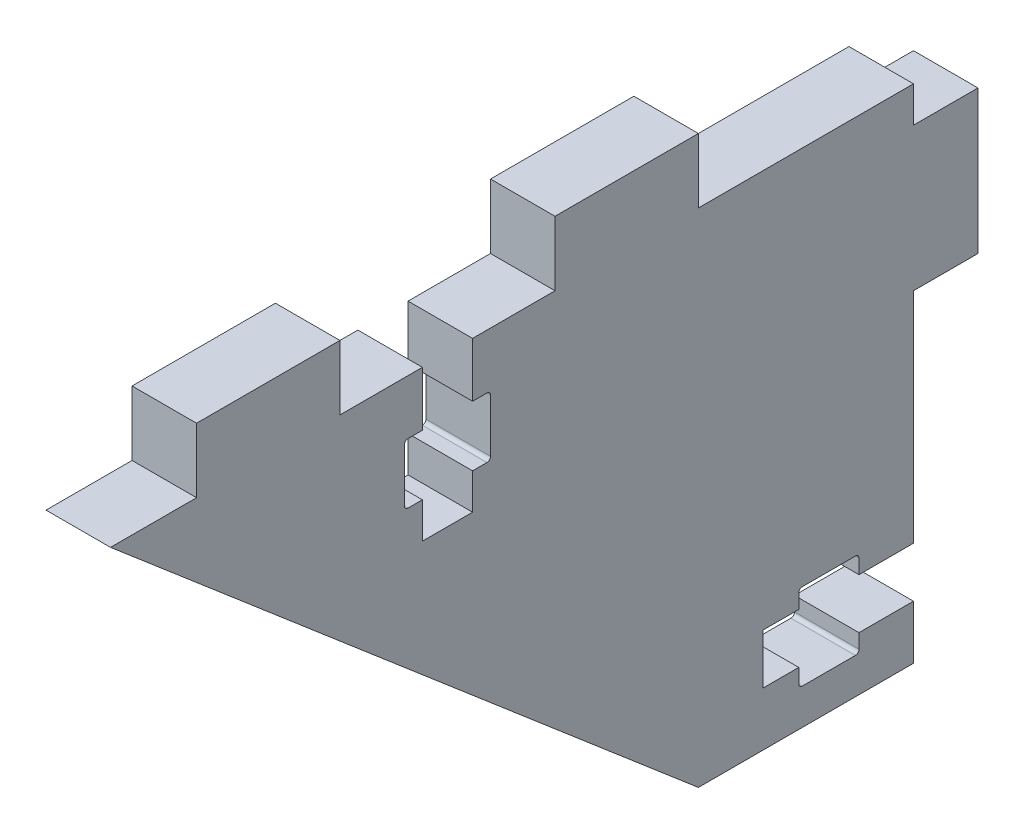
SolidWorks part; units mm, degrees
ref_plane "Front Plane" through (0, 0, 0) normal (0, 0, 1) x (1, 0, 0)
ref_plane "Top Plane" through (0, 0, 0) normal (0, 1, 0) x (1, 0, 0)
ref_plane "Right Plane" through (0, 0, 0) normal (1, 0, 0) x (0, 0, -1)
sketch "Sketch1" plane through (0, 0, 0) normal (1, 0, 0) x (0, 0, -1)
  line L0 (0, 0) -> (0, -35)
  line L1 (0, -35) -> (-56, 0)
  line L2 (-56, 0) -> (0, 0)
  dimension "D1" = 35
  dimension "D2" = 56
extrude "Boss-Extrude1" add sketch "Sketch1" along normal blind 4.5
sketch "Sketch2" plane through (4.5, 0, 0) normal (1, 0, 0) x (0, 0, -1)
  line L0 (0, -35) -> (0, 0) construction
  line L1 (-4.5, -2.5) -> (4.5, -2.5)
  line L2 (-4.5, -2.5) -> (-4.5, -12.5)
  line L3 (-4.5, -12.5) -> (4.5, -12.5)
  line L4 (4.5, -2.5) -> (4.5, -12.5)
  line L5 (-4.5, -2.5) -> (4.5, -12.5) construction
  line L6 (-4.5, -12.5) -> (4.5, -2.5) construction
  line L7 (0, 0) -> (-56, 0) construction
  point P0 (0, -7.5)
  dimension "D1" = 10
  dimension "D2" = 7.5
  dimension "D3" = 4.5
extrude "Boss-Extrude2" add sketch "Sketch2" against normal through all
sketch "Sketch3" plane through (4.5, 0, 0) normal (1, 0, 0) x (0, 0, -1)
  line L0 (0, -35) -> (-15, -35)
  line L1 (0, -25) -> (-56, 0)
  line L4 (0, -35) -> (0, -12.5) construction
  line L5 (0, -25) -> (0, -35)
  line L6 (-56, 0) -> (-15, -35)
  dimension "D1" = 15
  dimension "D2" = 10
extrude "Boss-Extrude3" add sketch "Sketch3" against normal through all
sketch "Sketch4" plane through (4.5, 0, 0) normal (1, 0, 0) x (0, 0, -1)
  line L0 (0, -29.5) -> (-10.5, -29.5) construction
  line L1 (0, -35) -> (0, -12.5) construction
  line L2 (0, -27.75) -> (-10.5, -27.75) construction
  line L3 (-10.5, -27.75) -> (-10.5, -31.25) construction
  line L4 (0, -31.25) -> (0, -27.75)
  line L5 (0, -27.75) -> (-3.8, -27.75)
  line L6 (-3.8, -27.75) -> (-3.8, -26.75)
  line L7 (-4.05, -26.5) -> (-7.75, -26.5)
  line L8 (-8, -26.75) -> (-8, -27.75)
  line L9 (-8, -27.75) -> (-10.5, -27.75)
  line L10 (-10.5, -27.75) -> (-10.5, -31.25)
  line L12 (0, -31.25) -> (-10.5, -31.25) construction
  line L13 (-8, -31.25) -> (-10.5, -31.25)
  line L14 (-8, -32.25) -> (-8, -31.25)
  line L15 (-4.05, -32.5) -> (-7.75, -32.5)
  line L16 (-3.8, -31.25) -> (-3.8, -32.25)
  line L17 (0, -31.25) -> (-3.8, -31.25)
  line L18 (4.5, -12.5) -> (4.5, -2.5) construction
  line L19 (0, -18.5) -> (-34.3286, -18.5) construction
  line L20 (-56, 0) -> (-15, -35) construction
  line L37 (0, -31.25) -> (-10.5, -31.25) construction
  arc A0 (-8, -32.25) -> (-7.75, -32.5) centre (-7.75, -32.25) ccw
  arc A1 (-4.05, -32.5) -> (-3.8, -32.25) centre (-4.05, -32.25) ccw
  arc A2 (-3.8, -26.75) -> (-4.05, -26.5) centre (-4.05, -26.75) ccw
  arc A3 (-7.75, -26.5) -> (-8, -26.75) centre (-7.75, -26.75) ccw
  point P10 (4.5, -7.5)
  point P20 (-8, -32.5)
  point P23 (-3.8, -32.5)
  point P26 (-3.8, -26.5)
  point P29 (-8, -26.5)
  dimension "D7" = 0.25
  dimension "D1" = 10.5
  dimension "D2" = 1.75
  dimension "D3" = 3
  dimension "D4" = 4.2
  dimension "D5" = 8
  dimension "D6" = 22
extrude "Cut-Extrude1" cut sketch "Sketch4" against normal through all
sketch "Sketch5" plane through (4.5, 0, 0) normal (1, 0, 0) x (0, 0, -1)
  line L0 (0, 0) -> (-56, 0) construction
  line L1 (-25, 4.5) -> (-15, 4.5)
  line L2 (-25, 4.5) -> (-25, -4.5)
  line L3 (-25, -4.5) -> (-15, -4.5)
  line L4 (-15, 4.5) -> (-15, -4.5)
  line L5 (-25, 4.5) -> (-15, -4.5) construction
  line L6 (-25, -4.5) -> (-15, 4.5) construction
  line L7 (-32.5, 0) -> (-32.5, 4.5) construction
  line L8 (-40, -4.5) -> (-50, 4.5) construction
  line L9 (-40, 4.5) -> (-50, -4.5) construction
  line L10 (-50, 4.5) -> (-50, -4.5)
  line L11 (-40, -4.5) -> (-50, -4.5)
  line L12 (-40, 4.5) -> (-40, -4.5)
  line L13 (-40, 4.5) -> (-50, 4.5)
  line L14 (-25, -4.5) -> (-15, 4.5) construction
  point P0 (-20, 0)
  point P14 (-45, 0)
  dimension "D3" = 4.5
  dimension "D1" = 20
  dimension "D2" = 10
  dimension "D4" = 25
extrude "Boss-Extrude4" add sketch "Sketch5" against normal through all
sketch "Sketch6" plane through (4.5, 0, 0) normal (1, 0, 0) x (0, 0, -1)
  line L0 (-32.5, 0) -> (-32.5, -10.5) construction
  line L1 (-25, 0) -> (-40, 0) construction
  line L2 (-30.75, -10.5) -> (-34.25, -10.5) construction
  line L3 (-34.25, -10.5) -> (-34.25, 0) construction
  line L4 (-30.75, 0) -> (-34.25, 0)
  line L5 (-34.25, 0) -> (-34.25, -3.8)
  line L6 (-34.25, -3.8) -> (-35.25, -3.8)
  line L7 (-35.5, -4.05) -> (-35.5, -7.75)
  line L8 (-35.25, -8) -> (-34.25, -8)
  line L9 (-34.25, -8) -> (-34.25, -10.5)
  line L10 (-34.25, -10.5) -> (-30.75, -10.5)
  line L11 (-30.75, -10.5) -> (-30.75, 0) construction
  line L12 (-30.75, -8) -> (-30.75, -10.5)
  line L13 (-29.75, -8) -> (-30.75, -8)
  line L14 (-29.5, -4.05) -> (-29.5, -7.75)
  line L15 (-30.75, -3.8) -> (-29.75, -3.8)
  line L16 (-30.75, 0) -> (-30.75, -3.8)
  arc A0 (-35.5, -7.75) -> (-35.25, -8) centre (-35.25, -7.75) ccw
  arc A1 (-35.25, -3.8) -> (-35.5, -4.05) centre (-35.25, -4.05) ccw
  arc A2 (-29.75, -3.8) -> (-29.5, -4.05) centre (-29.75, -4.05) cw
  arc A3 (-29.5, -7.75) -> (-29.75, -8) centre (-29.75, -7.75) cw
  point P12 (-35.5, -8)
  point P15 (-35.5, -3.8)
  point P26 (-29.5, -3.8)
  point P27 (-29.5, -8)
  dimension "D1" = 10.5
  dimension "D2" = 1.75
  dimension "D4" = 4.2
  dimension "D6" = 0.25
  dimension "D3" = 8
  dimension "D5" = 3
extrude "Cut-Extrude2" cut sketch "Sketch6" against normal through all
sketch "Sketch8" [suppressed] plane through (4.5, 0, 0) normal (1, 0, 0) x (0, 0, -1)
  line L0 (-15, -30) -> (-27, -30) construction
  line L1 (-15, -35) -> (-27, -35)
  line L2 (-15, -25) -> (-27, -25)
  line L3 (-15, -35) -> (0, -35) construction
  line L4 (-15, -25) -> (-15, -35)
  arc A1 (-27, -25) -> (-27, -35) centre (-27, -30) ccw
  dimension "D5" = 5
  dimension "D1" = 0
  dimension "D2" = 12
  dimension "D3" = 0
  dimension "D4" = 10
extrude "Boss-Extrude5" [suppressed] add sketch "Sketch8" against normal up to surface (4.5 mm away) up to face at (0, -13.4542, 19.4542)
sketch "Sketch9" [suppressed] plane through (4.5, 0, 0) normal (1, 0, 0) x (0, 0, -1)
  line L0 (-27, -30) -> (-22, -30) construction
  line L1 (-27, -27) -> (-22, -27)
  line L2 (-27, -33) -> (-22, -33)
  arc A0 (-27, -27) -> (-27, -33) centre (-27, -30) ccw
  arc A1 (-22, -33) -> (-22, -27) centre (-22, -30) ccw
  point P3 (-24.5, -30)
  dimension "D1" = 3
  dimension "D2" = 5
extrude "Cut-Extrude3" [suppressed] cut sketch "Sketch9" against normal through all
equation "\"X-ROD-SPACING\"=45"
equation "\"Y-ROD-SPACING\"=75"
equation "\"Z-ROD-SPACING\"=17.5"
equation "\"Y-BED-OFFSET\"=2"
equation "\"Y-BED-ROD-INSET\"=3.5"
equation "\"Y-BED-SCREW-SPACING\"=209"
equation "\"Y-BED-SCREW-CUTOUT-SLOT-HEIGHT\"=1"
equation "\"T-SLOT-NUT-FILLET-RADIUS\"=0.25"
equation "\"T-SLOT-SCREW-SHAFT-RADIUS\"=1.75"
equation "\"T-SLOT-SCREW-SHAFT-CUTOUT-LENGTH\"=10.5"
equation "\"T-SLOT-NUT-DEPTH\"=4.2"
equation "\"T-SLOT-NUT-WIDTH\"=3"
equation "\"T-SLOT-NUT-END-DISTANCE\"=8"
equation "\"ACRYLIC-THICKNESS\"=10"
equation "\"ACRYLIC-THICKNESS2\"=4.5"
equation "\"ACRYLIC-TAB-CUTOUT-SIZE\"=\"ACRYLIC-THICKNESS\"+\"ACRYLIC-TAB-TOLERANCE\"*2"
equation "\"ACRYLIC-TAB-WIDTH\"=\"ACRYLIC-THICKNESS\""
equation "\"ACRYLIC-M3-HOLE\"=3.1"
equation "\"SMOOTHROD-CAP-SCREW-DISTANCE\"=20"
equation "\"FRAME-WIDTH-INNER\"=370"
equation "\"NEMA17-HOLE-SPACING\"=31"
equation "\"NEMA17-CENTRAL-CUTOUT\"=22.5"
equation "\"Z-BRACKET-REACH\"=55"
equation "\"Z-ROD-INSET\"=16"
equation "\"TOP-BRACKET-SPACING\"=40"
equation "\"SMOOTHROD-X-LENGTH\"=350"
equation "\"SMOOTHROD-Y-LENGTH\"=350"
equation "\"SMOOTHROD-Z-LENGTH\"=350"
equation "\"SMOOTHROD-TIGHTENING-HEADROOM\"=1"
equation "\"LEADSCREW-Z-LENGTH\"=300"
equation "\"SCREW-LENGTH-FRAME\"=\"ACRYLIC-THICKNESS\" + 10"
equation "\"SCREW-LENGTH-MOTOR\"=\"ACRYLIC-THICKNESS\" + 5"
equation "\"SCREW-LENGTH-EXTRUDER\"=28"
equation "\"SCREW-HEAD-RADIUS\"=6"
equation "\"PRINTED-X-SMOOTHROD-DIAMETER\"=8.2"
equation "\"PRINTED-X-SMOOTHROD-CUTOUT\"=10"
equation "\"PRINTED-X-BASE-HEIGHT\"=10"
equation "\"PRINTED-LM8UU-CUTOUT-SIZE\"=15.25"
equation "\"PRINTED-LM8UU-CUTOUT-LENGTH\"=24.5"
equation "\"PRINTED-X-IDLER-HEIGHT\"=16"
equation "\"PSU-MOUNTING-WIDTH\"=95"
equation "\"PSU-MOUNTING-HEIGHT\"=177"
equation "\"Y-BELT-TO-ROD-DISTANCE\"=20"
equation "\"SPOOL-HOLDER-ROD-SPACING\"=150"
equation "\"ACRYLIC-X-CARRIAGE-WIDTH\"=55"
equation "\"ACRYLIC-X-CARRIAGE-HEIGHT\"=75"
equation "\"ACRYLIC-X-CARRIAGE-SCREW-SPACING-X\"=15"
equation "\"ACRYLIC-X-CARRIAGE-SCREW-SPACING-Y\"=33"
equation "\"ACRYLIC-X-CARRIAGE-CENTER-TAB-SPACING\"=14"
equation "\"ACRYLIC-X-CARRIAGE-EXTRUDER-SHELF-DEPTH\"=\"ACRYLIC-X-CARRIAGE-EXTRUDER-OFFSET\" + 30"
equation "\"D2@Sketch1\"=\"ACRYLIC-X-CARRIAGE-EXTRUDER-SHELF-DEPTH\""
equation "\"D1@Boss-Extrude1\"=\"ACRYLIC-THICKNESS2\""
equation "\"D1@Sketch2\"=\"ACRYLIC-TAB-WIDTH\""
equation "\"D3@Sketch2\"=\"ACRYLIC-THICKNESS2\""
equation "\"ACRYLIC-X-CARRIAGE-LM8UU-CUTOUT-WIDTH\"=24.25"
equation "\"ACRYLIC-X-CARRIAGE-EXTRUDER-BRACE-SPACING\"=23"
equation "\"ACRYLIC-X-CARRIAGE-EXTRUDER-BRACE-HEIGHT\"=35"
equation "\"D1@Sketch1\"=\"ACRYLIC-X-CARRIAGE-EXTRUDER-BRACE-HEIGHT\""
equation "\"D1@Sketch4\"=\"T-SLOT-SCREW-SHAFT-CUTOUT-LENGTH\""
equation "\"D2@Sketch4\"=\"T-SLOT-SCREW-SHAFT-RADIUS\""
equation "\"D3@Sketch4\"=\"T-SLOT-NUT-WIDTH\""
equation "\"D4@Sketch4\"=\"T-SLOT-NUT-DEPTH\""
equation "\"D5@Sketch4\"=\"T-SLOT-NUT-END-DISTANCE\""
equation "\"D7@Sketch4\"=\"T-SLOT-NUT-FILLET-RADIUS\""
equation "\"ACRYLIC-X-CARRIAGE-EXTRUDER-BRACE-SCREW-SPACING\"=22"
equation "\"D6@Sketch4\"=\"ACRYLIC-X-CARRIAGE-EXTRUDER-BRACE-SCREW-SPACING\""
equation "\"ACRYLIC-X-CARRIAGE-EXTRUDER-BRACE-TAB-OFFSET\"=20"
equation "\"D1@Sketch5\"=\"ACRYLIC-X-CARRIAGE-EXTRUDER-BRACE-TAB-OFFSET\""
equation "\"D2@Sketch5\"=\"ACRYLIC-TAB-WIDTH\""
equation "\"D3@Sketch5\"=\"ACRYLIC-THICKNESS2\""
equation "\"ACRYLIC-X-CARRIAGE-EXTRUDER-OFFSET\"=26"
equation "\"ACRYLIC-X-CARRIAGE-EXTRUDER-ANGLE\"=90"
equation "\"D1@Sketch6\"=\"T-SLOT-SCREW-SHAFT-CUTOUT-LENGTH\""
equation "\"D2@Sketch6\"=\"T-SLOT-SCREW-SHAFT-RADIUS\""
equation "\"D3@Sketch6\"=\"T-SLOT-NUT-END-DISTANCE\""
equation "\"D4@Sketch6\"=\"T-SLOT-NUT-DEPTH\""
equation "\"D5@Sketch6\"=\"T-SLOT-NUT-WIDTH\""
equation "\"D6@Sketch6\"=\"T-SLOT-NUT-FILLET-RADIUS\""
